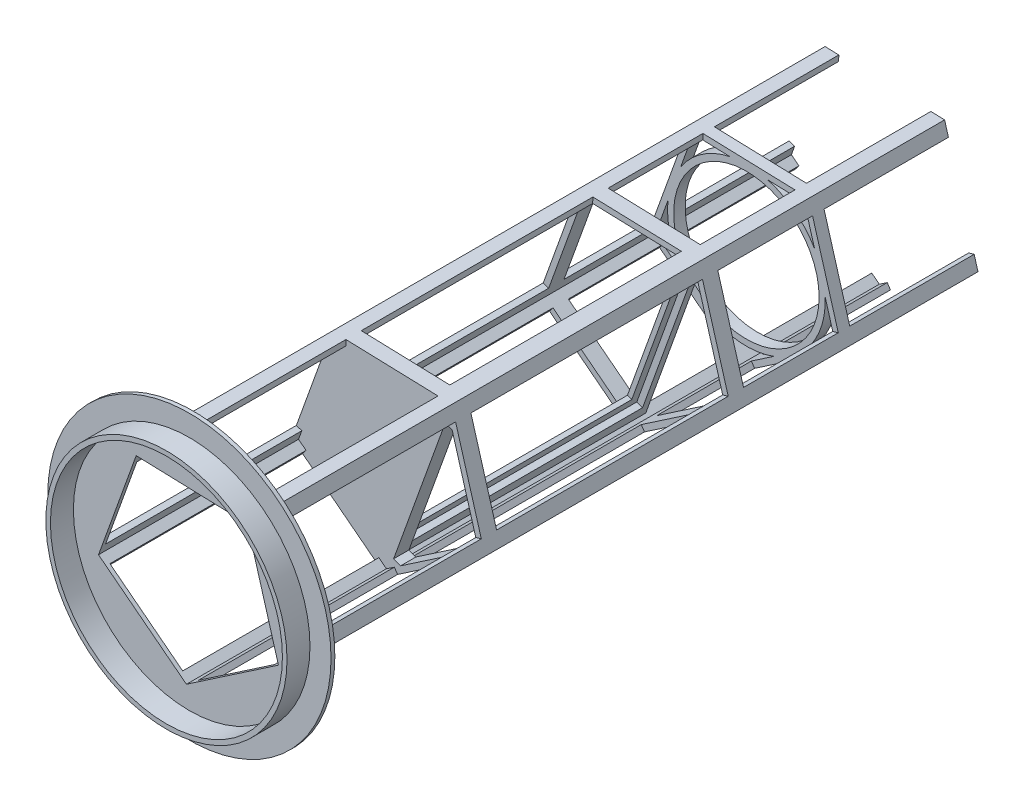
SolidWorks part; units mm, degrees
ref_plane "Front Plane" through (0, 0, 0) normal (0, 0, 1) x (1, 0, 0)
ref_plane "Top Plane" through (0, 0, 0) normal (0, 1, 0) x (1, 0, 0)
ref_plane "Right Plane" through (0, 0, 0) normal (1, 0, 0) x (0, 0, -1)
sketch "Sketch3" plane through (0, 0, 0) normal (0, 0, 1) x (1, 0, 0)
  line L0 (0, 0) -> (16.2851, 21.0012) construction
  line L1 (15.1489, 19.536) -> (-13.8986, 20.4445)
  line L2 (-13.8986, 20.4445) -> (-23.7387, -6.9006)
  line L3 (-23.7387, -6.9006) -> (-0.7728, -24.7093)
  line L4 (-0.7728, -24.7093) -> (23.2611, -8.3705)
  line L5 (0, 0) -> (29.9163, 0) construction
  line L6 (0, 0) -> (25.0057, -8.9983) construction
  line L10 (-0.8307, -26.5625) -> (25.0057, -8.9983)
  line L11 (25.0057, -8.9983) -> (16.2851, 21.0012)
  line L12 (16.2851, 21.0012) -> (-14.941, 21.9778)
  line L13 (-14.941, 21.9778) -> (-25.5191, -7.4182)
  line L14 (-25.5191, -7.4182) -> (-0.8307, -26.5625)
  line L15 (23.2611, -8.3705) -> (15.1489, 19.536)
  circle A0 centre (0, 0) radius 20 construction
  dimension "D2" = 40
extrude "Boss-Extrude2" add sketch "Sketch3" along normal blind 185
ref_plane "Plane1" through (0, 0, 92.5) normal (0, 0, 1) x (1, 0, 0)
sketch "Sketch4" plane through (0, 0, 0) normal (0, 0, -1) x (-1, 0, 0)
  line L0 (14.745, 18.0921) -> (16.1564, 18.6)
  line L1 (13.8986, 20.4445) -> (23.7387, -6.9006) construction
  line L2 (14.941, 21.9778) -> (25.5191, -7.4182) construction
  line L3 (24.3036, -4.0404) -> (22.8922, -4.5483)
  line L4 (22.8922, -4.5483) -> (14.745, 18.0921)
  line L5 (24.3036, -4.0404) -> (16.1564, 18.6)
  dimension "D1" = 2.5
  dimension "D2" = 2.5
extrude "Cut-Extrude1" cut sketch "Sketch4" against normal offset from surface (180 mm away) 5 up to face at (0, 0, 185)
ref_point "Point1"
ref_axis "Axis1" through (0, 0, 185) along (0, 0, 1)
pattern_circular "CirPattern1" count 5 over 360 about axis through (0, 0, 185) along (0, 0, 1) of "Cut-Extrude1"
ref_plane "Plane2" through (0, 0, 92.5) normal (0, 0, 1) x (1, 0, 0)
sketch "Sketch5" plane through (0, 0, 92.5) normal (0, 0, 1) x (1, 0, 0)
  line L0 (-2.0696, -25.6018) -> (14.7182, 21.0502) construction
  line L2 (-24.1133, -8.5083) -> (-1.8275, -25.7895) construction
  line L3 (23.2611, -8.3705) -> (0, 0) construction
  line L4 (-4.3961, -23.7977) -> (11.7756, 21.1422)
  line L8 (-2.0696, -25.6018) -> (-4.3961, -23.7977)
  line L10 (14.7182, 21.0502) -> (11.7756, 21.1422)
  line L11 (-2.0696, -25.6018) -> (14.7182, 21.0502)
  line L12 (-22.8004, 22.2236) -> (6.2471, 21.3151) construction
  dimension "D1" = 18
  dimension "D2" = 2.8
extrude "Boss-Extrude3" add sketch "Sketch5" along normal mid plane 64.5
sketch "Sketch6" plane through (0, 0, 124.75) normal (0, 0, 1) x (1, 0, 0)
  line L5 (-25.5191, -7.4182) -> (-0.8307, -26.5625)
  line L6 (-0.8307, -26.5625) -> (25.0057, -8.9983)
  line L7 (25.0057, -8.9983) -> (16.2851, 21.0012)
  line L8 (16.2851, 21.0012) -> (-14.941, 21.9778)
  line L9 (-14.941, 21.9778) -> (-25.5191, -7.4182)
  line L10 (-25.5191, -7.4182) -> (-0.8307, -26.5625)
  line L11 (-0.8307, -26.5625) -> (25.0057, -8.9983)
  line L12 (25.0057, -8.9983) -> (16.2851, 21.0012)
  line L13 (16.2851, 21.0012) -> (-14.941, 21.9778)
  line L14 (-14.941, 21.9778) -> (-25.5191, -7.4182)
  dimension "D1" = 0
extrude "Boss-Extrude4" add sketch "Sketch6" along normal blind 4
sketch "Sketch7" plane through (0, 0, 124.75) normal (0, 0, -1) x (-1, 0, 0)
  line L0 (-3.6897, -1.3278) -> (20.23, 7.2798) construction
  line L1 (-11.7756, 21.1422) -> (4.3961, -23.7977) construction
  line L2 (16.1564, 18.6) -> (24.3036, -4.0404) construction
  line L4 (19.0326, -2.4504) -> (13.1071, 14.0159)
  line L5 (0.2139, -9.2223) -> (-5.7115, 7.244)
  line L7 (19.0326, -2.4504) -> (-5.7115, 7.244) construction
  line L8 (0.2139, -9.2223) -> (13.1071, 14.0159) construction
  line L9 (9.6232, -5.8364) -> (3.6978, 10.63) construction
  line L11 (-11.7756, 21.1422) -> (4.3961, -23.7977) construction
  arc A0 (-5.7115, 7.244) -> (13.1071, 14.0159) centre (3.6978, 10.63) cw
  arc A1 (0.2139, -9.2223) -> (19.0326, -2.4504) centre (9.6232, -5.8364) ccw
  point P7 (6.6605, 2.3968)
  point P9 (13.0092, -15.2457)
  point P14 (0.3119, 20.0393)
  dimension "D1" = 37.5
  dimension "D2" = 20
  dimension "D3" = 1
extrude "Cut-Extrude2" cut sketch "Sketch7" against normal blind 2
sketch "Sketch8" plane through (6.3243, -2.2758, 0) normal (0.9409, -0.3386, 0) x (0, 0, -1)
  line L0 (-60.25, 0) -> (-124.75, 0) construction
  line L1 (-124.75, -23.2131) -> (-124.75, 23.2131) construction
  line L3 (-60.25, -23.2131) -> (-60.25, 23.2131) construction
  line L5 (-123, -20.5) -> (-123, 20.5)
  line L6 (-123, -20.5) -> (-62, -20.5)
  line L7 (-123, 20.5) -> (-62, 20.5)
  line L8 (-62, -20.5) -> (-62, 20.5)
  line L14 (-62, 20.5) -> (-123, -20.5) construction
  line L15 (-62, -20.5) -> (-123, 20.5) construction
  point P11 (-92.5, 0)
  point P14 (-92.5, 0)
  dimension "D1" = 61
  dimension "D2" = 41
extrude "Cut-Extrude3" cut sketch "Sketch8" against normal blind 1.6
sketch "Sketch9" plane through (4.8189, -1.7341, 0) normal (0.9409, -0.3386, 0) x (0, 0, -1)
  line L8 (-121, -18.5) -> (-64, -18.5)
  line L9 (-64, -18.5) -> (-64, 18.5)
  line L10 (-64, 18.5) -> (-121, 18.5)
  line L11 (-121, 18.5) -> (-121, -18.5)
  line L12 (-121, -18.5) -> (-64, -18.5)
  line L13 (-64, -18.5) -> (-64, 18.5)
  line L14 (-64, 18.5) -> (-121, 18.5)
  line L15 (-121, 18.5) -> (-121, -18.5)
  dimension "D1" = 2
extrude "Cut-Extrude4" cut sketch "Sketch9" against normal up to surface (1.2 mm away) up to face at (3.6897, -1.3278, 92.5)
sketch "Sketch10" plane through (0, 0, 60.25) normal (0, 0, -1) x (-1, 0, 0)
  line L25 (-23.2611, -8.3705) -> (0.7728, -24.7093)
  line L26 (0.7728, -24.7093) -> (23.7387, -6.9006)
  line L27 (23.7387, -6.9006) -> (13.8986, 20.4445)
  line L28 (13.8986, 20.4445) -> (-15.1489, 19.536)
  line L29 (-15.1489, 19.536) -> (-23.2611, -8.3705)
  line L30 (0.8307, -26.5625) -> (25.5191, -7.4182)
  line L31 (-25.0057, -8.9983) -> (0.8307, -26.5625)
  line L32 (-16.2851, 21.0012) -> (-25.0057, -8.9983)
  line L33 (14.941, 21.9778) -> (-16.2851, 21.0012)
  line L34 (25.5191, -7.4182) -> (14.941, 21.9778)
  line L40 (0.8307, -26.5625) -> (25.5191, -7.4182)
  line L41 (-25.0057, -8.9983) -> (0.8307, -26.5625)
  line L42 (-16.2851, 21.0012) -> (-25.0057, -8.9983)
  line L43 (14.941, 21.9778) -> (-16.2851, 21.0012)
  line L44 (25.5191, -7.4182) -> (14.941, 21.9778)
  dimension "D1" = 0
extrude "Boss-Extrude5" add sketch "Sketch10" against normal blind 4
sketch "Sketch11" plane through (0, 0, 60.25) normal (0, 0, -1) x (-1, 0, 0)
  line L0 (3.8621, -22.3137) -> (4.3961, -23.7977)
  line L1 (4.3961, -23.7977) -> (3.6676, -24.3627)
  line L2 (-11.2416, 19.6582) -> (-11.7756, 21.1422)
  line L3 (-11.7756, 21.1422) -> (-12.697, 21.1134)
  line L4 (21.7631, -8.4326) -> (3.8621, -22.3137)
  line L7 (3.8621, -22.3137) -> (-11.2416, 19.6582)
  line L9 (-14.1842, 19.5662) -> (1.5355, -24.1178)
  line L10 (-14.1842, 19.5662) -> (1.5355, -24.1178)
  line L11 (-12.697, 21.1134) -> (11.3529, 21.8656) construction
  line L13 (3.8621, -22.3137) -> (-11.2416, 19.6582) construction
  line L18 (22.6823, -9.618) -> (3.6676, -24.3627) construction
  line L19 (3.8621, -22.3137) -> (-11.2416, 19.6582)
  line L27 (-11.2416, 19.6582) -> (11.3998, 20.3663)
  line L31 (1.5355, -24.1178) -> (2.7484, -23.1773)
  line L33 (1.5355, -24.1178) -> (2.7484, -23.1773)
  line L35 (2.7484, -23.1773) -> (3.6676, -24.3627)
  line L37 (2.7484, -23.1773) -> (3.6676, -24.3627)
  line L39 (3.6676, -24.3627) -> (22.6823, -9.618)
  line L41 (22.6823, -9.618) -> (21.7631, -8.4326)
  line L43 (11.3998, 20.3663) -> (11.3529, 21.8656)
  line L45 (11.3529, 21.8656) -> (-12.697, 21.1134)
  line L47 (-12.697, 21.1134) -> (-12.6502, 19.6141)
  line L48 (-12.697, 21.1134) -> (-12.6502, 19.6141)
  line L49 (-12.6502, 19.6141) -> (-14.1842, 19.5662)
  line L50 (-12.6502, 19.6141) -> (-14.1842, 19.5662)
  dimension "D1" = 0
ref_plane "Plane3" through (0, 0, 32.5) normal (0, 0, 1) x (1, 0, 0)
sketch "Sketch14" plane through (0, 0, 32.5) normal (0, 0, 1) x (1, 0, 0)
  line L5 (-25.5191, -7.4182) -> (-0.8307, -26.5625)
  line L6 (-0.8307, -26.5625) -> (25.0057, -8.9983)
  line L7 (25.0057, -8.9983) -> (16.2851, 21.0012)
  line L8 (16.2851, 21.0012) -> (-14.941, 21.9778)
  line L9 (-14.941, 21.9778) -> (-25.5191, -7.4182)
  line L11 (-0.8307, -26.5625) -> (25.0057, -8.9983)
  line L12 (25.0057, -8.9983) -> (16.2851, 21.0012)
  line L16 (23.2611, -8.3705) -> (15.3259, -13.7651)
  line L18 (-0.7728, -24.7093) -> (-8.3554, -18.8294)
  line L20 (-23.7387, -6.9006) -> (-20.4898, 2.1279)
  line L22 (-13.8986, 20.4445) -> (-4.308, 20.1445)
  line L24 (15.1489, 19.536) -> (17.8273, 10.3221)
  line L25 (7.1625, -19.3147) -> (-0.7728, -24.7093)
  line L26 (20.5827, 0.8433) -> (23.2611, -8.3705)
  line L27 (5.5584, 19.8359) -> (15.1489, 19.536)
  line L28 (-17.1475, 11.416) -> (-13.8986, 20.4445)
  line L29 (-16.1561, -12.7805) -> (-23.7387, -6.9006)
  line L30 (16.2851, 21.0012) -> (-14.941, 21.9778)
  line L31 (-14.941, 21.9778) -> (-25.5191, -7.4182)
  line L32 (-25.5191, -7.4182) -> (-0.8307, -26.5625)
  circle A3 centre (0, 0) radius 19
  arc A8 (15.3259, -13.7651) -> (20.5827, 0.8433) centre (0, 0) ccw
  circle A9 centre (0, 0) radius 20.6 construction
  arc A10 (17.8273, 10.3221) -> (5.5584, 19.8359) centre (0, 0) ccw
  arc A11 (-4.308, 20.1445) -> (-17.1475, 11.416) centre (0, 0) ccw
  arc A12 (-20.4898, 2.1279) -> (-16.1561, -12.7805) centre (0, 0) ccw
  arc A13 (-8.3554, -18.8294) -> (7.1625, -19.3147) centre (0, 0) ccw
  dimension "D2" = 38
  dimension "D1" = 0
  dimension "D3" = 1.6
extrude "Boss-Extrude8" add sketch "Sketch14" along normal blind 3
ref_plane "Plane4" through (0, 0, 29.5) normal (0, 0, -1) x (-1, 0, 0)
sketch "Sketch15" plane through (0, 0, 29.5) normal (0, 0, -1) x (-1, 0, 0)
  line L0 (-23.2611, -8.3705) -> (0.7728, -24.7093)
  line L1 (0.7728, -24.7093) -> (23.7387, -6.9006)
  line L2 (23.7387, -6.9006) -> (13.8986, 20.4445)
  line L3 (13.8986, 20.4445) -> (-15.1489, 19.536)
  line L4 (-15.1489, 19.536) -> (-23.2611, -8.3705)
  line L5 (0.8307, -26.5625) -> (25.5191, -7.4182)
  line L6 (-25.0057, -8.9983) -> (0.8307, -26.5625)
  line L7 (-16.2851, 21.0012) -> (-25.0057, -8.9983)
  line L8 (14.941, 21.9778) -> (-16.2851, 21.0012)
  line L9 (25.5191, -7.4182) -> (14.941, 21.9778)
  line L10 (0.8307, -26.5625) -> (25.5191, -7.4182)
  line L11 (-25.0057, -8.9983) -> (0.8307, -26.5625)
  line L12 (-16.2851, 21.0012) -> (-25.0057, -8.9983)
  line L13 (14.941, 21.9778) -> (-16.2851, 21.0012)
  line L14 (25.5191, -7.4182) -> (14.941, 21.9778)
  dimension "D1" = 0
sketch "Sketch29" plane through (0, 0, 185) normal (0, 0, 1) x (1, 0, 0)
  line L5 (-25.5191, -7.4182) -> (-0.8307, -26.5625)
  line L6 (-0.8307, -26.5625) -> (25.0057, -8.9983)
  line L7 (25.0057, -8.9983) -> (16.2851, 21.0012)
  line L8 (16.2851, 21.0012) -> (-14.941, 21.9778)
  line L9 (-14.941, 21.9778) -> (-25.5191, -7.4182)
  line L10 (-25.5191, -7.4182) -> (-0.8307, -26.5625)
  line L11 (-0.8307, -26.5625) -> (25.0057, -8.9983)
  line L12 (25.0057, -8.9983) -> (16.2851, 21.0012)
  line L13 (16.2851, 21.0012) -> (-14.941, 21.9778)
  line L14 (-14.941, 21.9778) -> (-25.5191, -7.4182)
  dimension "D1" = 0
extrude "Boss-Extrude13" add sketch "Sketch29" along normal blind 2
sketch "Sketch30" plane through (0, 0, 187) normal (0, 0, 1) x (1, 0, 0)
  line L0 (25.0057, -8.9983) -> (-20.23, 7.2798) construction
  line L1 (-14.941, 21.9778) -> (-25.5191, -7.4182) construction
  line L2 (3.1542, -17.0767) -> (-13.3121, -11.1513)
  line L3 (18.5086, -9.8487) -> (20.5401, -4.2031)
  line L4 (-20.5401, 4.2031) -> (-18.5086, 9.8487)
  line L5 (13.3121, 11.1513) -> (-3.1542, 17.0767)
  line L6 (14.4454, -21.1398) -> (-14.4454, 21.1398) construction
  line L7 (-24.6033, -7.0881) -> (24.6033, 7.0881) construction
  line L8 (19.5243, -7.0259) -> (-19.5243, 7.0259) construction
  arc A0 (18.5086, -9.8487) -> (3.1542, -17.0767) centre (7.2174, -5.7855) cw
  arc A1 (-18.5086, 9.8487) -> (-3.1542, 17.0767) centre (-7.2174, 5.7855) cw
  arc A2 (-13.3121, -11.1513) -> (-20.5401, 4.2031) centre (-9.2489, 0.1399) cw
  arc A3 (20.5401, -4.2031) -> (13.3121, 11.1513) centre (9.2489, -0.1399) ccw
  point P5 (0, 0)
  dimension "D3" = 12
  dimension "D1" = 30
  dimension "D2" = 41.5
extrude "Cut-Extrude8" [suppressed] cut sketch "Sketch30" against normal blind 0.6
sketch "Sketch31" [suppressed] plane through (0, 0, 186.4) normal (0, 0, 1) x (1, 0, 0)
  line L0 (25.0057, -8.9983) -> (0, 0) construction
  line L1 (12.0432, 0.9801) -> (8.6573, -8.4292)
  line L2 (12.0432, 0.9801) -> (-8.6573, 8.4292)
  line L3 (8.6573, -8.4292) -> (-12.0432, -0.9801)
  line L4 (-8.6573, 8.4292) -> (-12.0432, -0.9801)
  line L5 (12.0432, 0.9801) -> (-12.0432, -0.9801) construction
  line L6 (8.6573, -8.4292) -> (-8.6573, 8.4292) construction
  line L7 (-10.3503, 3.7246) -> (10.3503, -3.7246) construction
  dimension "D1" = 22
  dimension "D2" = 10
extrude "Cut-Extrude9" [suppressed] cut sketch "Sketch31" against normal up to surface (1.4 mm away) up to face at (0, 0, 185)
sketch "Sketch32" [suppressed] plane through (0, 0, 187) normal (0, 0, 1) x (1, 0, 0)
  line L0 (0, 0) -> (-36.3954, 13.0969) construction
  line L1 (-22.7695, 0.2228) -> (-21.2398, -0.3276)
  line L3 (-14.941, 21.9778) -> (-25.5191, -7.4182) construction
  line L4 (-17.6906, 14.3368) -> (-16.1609, 13.7863)
  line L5 (-18.5086, 9.8487) -> (-20.5401, 4.2031) construction
  line L6 (-18.5086, 9.8487) -> (-20.5401, 4.2031)
  line L7 (-17.6906, 14.3368) -> (-22.7695, 0.2228)
  arc A0 (-20.5401, 4.2031) -> (-13.3121, -11.1513) centre (-9.2489, 0.1399) ccw construction
  arc A1 (-20.5401, 4.2031) -> (-13.3121, -11.1513) centre (-9.2489, 0.1399) ccw construction
  arc A3 (-3.1542, 17.0767) -> (-18.5086, 9.8487) centre (-7.2174, 5.7855) ccw construction
  arc A4 (-16.1609, 13.7863) -> (-18.5086, 9.8487) centre (-7.2174, 5.7855) ccw
  arc A5 (-20.5401, 4.2031) -> (-21.2398, -0.3276) centre (-9.2489, 0.1399) ccw
  dimension "D1" = 7.5
extrude "Cut-Extrude11" [suppressed] cut sketch "Sketch32" against normal up to surface (0.6 mm away) up to face at (-13.7489, 20.2244, 0)
sketch "Sketch34" [suppressed] plane through (0, 0, 186.4) normal (0, 0, 1) x (1, 0, 0)
  line L0 (-22.7695, 0.2228) -> (-17.6906, 14.3368)
  line L1 (-22.7695, 0.2228) -> (-22.0638, -0.0311)
  line L2 (-17.6906, 14.3368) -> (-16.9849, 14.0828)
  line L3 (-22.0638, -0.0311) -> (-16.9849, 14.0828)
  line L4 (-13.3121, -11.1513) -> (3.1542, -17.0767)
  line L5 (18.5086, -9.8487) -> (20.5401, -4.2031)
  line L6 (13.3121, 11.1513) -> (-3.1542, 17.0767)
  line L7 (-18.5086, 9.8487) -> (-20.5401, 4.2031)
  line L8 (-13.3121, -11.1513) -> (3.1542, -17.0767) construction
  line L9 (18.5086, -9.8487) -> (20.5401, -4.2031) construction
  line L10 (13.3121, 11.1513) -> (-3.1542, 17.0767) construction
  line L11 (-18.5086, 9.8487) -> (-20.5401, 4.2031) construction
  arc A4 (3.1542, -17.0767) -> (18.5086, -9.8487) centre (7.2174, -5.7855) ccw
  arc A5 (20.5401, -4.2031) -> (13.3121, 11.1513) centre (9.2489, -0.1399) ccw
  arc A6 (-3.1542, 17.0767) -> (-18.5086, 9.8487) centre (-7.2174, 5.7855) ccw
  arc A7 (-20.5401, 4.2031) -> (-13.3121, -11.1513) centre (-9.2489, 0.1399) ccw
  arc A8 (3.1542, -17.0767) -> (18.5086, -9.8487) centre (7.2174, -5.7855) ccw construction
  arc A9 (20.5401, -4.2031) -> (13.3121, 11.1513) centre (9.2489, -0.1399) ccw construction
  arc A10 (-3.1542, 17.0767) -> (-18.5086, 9.8487) centre (-7.2174, 5.7855) ccw construction
  arc A11 (-20.5401, 4.2031) -> (-13.3121, -11.1513) centre (-9.2489, 0.1399) ccw construction
  dimension "D1" = 0
sketch "Sketch38" plane through (0, 0, 124.75) normal (0, 0, -1) x (-1, 0, 0)
  line L5 (13.8986, 20.4445) -> (-15.1489, 19.536)
  line L6 (-15.1489, 19.536) -> (-23.2611, -8.3705)
  line L7 (-23.2611, -8.3705) -> (0.7728, -24.7093)
  line L8 (0.7728, -24.7093) -> (23.7387, -6.9006)
  line L9 (23.7387, -6.9006) -> (13.8986, 20.4445)
  line L11 (-16.3988, 15.2363) -> (-23.2611, -8.3705)
  line L12 (-23.2611, -8.3705) -> (-2.9303, -22.1919)
  line L16 (-1.0956, -21.5316) -> (-2.9303, -22.1919)
  line L17 (0.03, -24.6596) -> (-15.6897, 19.0244)
  line L18 (-1.0956, -21.5316) -> (-14.5641, 15.8965)
  line L19 (-14.5641, 15.8965) -> (-16.3988, 15.2363)
  dimension "D3" = 1.6
  dimension "D4" = 1.6
  dimension "D1" = 0
  dimension "D2" = 1.6
extrude "Cut-Extrude14" cut sketch "Sketch38" against normal up to surface (4 mm away) up to face at (0, 0, 128.75)
sketch "Sketch40" plane through (-18.8186, 6.7719, 0) normal (0.9409, -0.3386, 0) x (0, 0, -1)
  line L0 (-185, 14.5309) -> (-185, -14.5309) construction
  line L1 (-185, 7.5) -> (-183.5, 7.5)
  line L2 (-185, 7.5) -> (-185, -7.5)
  line L3 (-185, -7.5) -> (-183.5, -7.5)
  line L4 (-183.5, 7.5) -> (-183.5, -7.5)
  line L5 (-183.5, 0) -> (-185, 0) construction
  point P9 (-185, 0)
  dimension "D1" = 15
  dimension "D2" = 1.5
ref_plane "Plane5" through (14.5641, 15.8965, 124.75) normal (0.3386, 0.9409, 0) x (0.9409, -0.3386, 0)
sketch "Sketch42" plane through (0, 0, 128.75) normal (0, 0, 1) x (1, 0, 0)
  line L0 (-20.23, 7.2798) -> (0, 0) construction
  line L1 (-16.1564, 18.6) -> (-24.3036, -4.0404) construction
  line L2 (5.4365, -16.774) -> (-14.8782, -9.4637) construction
  line L3 (5.4365, -16.774) -> (14.8782, 9.4637) construction
  line L4 (-14.8782, -9.4637) -> (-5.4365, 16.774) construction
  line L5 (14.8782, 9.4637) -> (-5.4365, 16.774) construction
  line L6 (5.4365, -16.774) -> (-5.4365, 16.774) construction
  line L7 (-14.8782, -9.4637) -> (14.8782, 9.4637) construction
  line L8 (-3.9066, 13.524) -> (11.6282, 7.9338) construction
  line L9 (4.7208, 13.1189) -> (-4.7208, -13.1189) construction
  line L10 (2.2472, -13.2032) -> (-10.1449, -8.7439) construction
  line L11 (-1.5355, -24.1178) -> (14.1842, 19.5662) construction
  line L12 (-1.5355, -24.1178) -> (14.1842, 19.5662)
  line L13 (12.891, 3.9416) -> (6.1392, -14.8212) construction
  line L14 (12.891, 3.9416) -> (10.6328, 4.7542) construction
  line L15 (6.1392, -14.8212) -> (3.881, -14.0086) construction
  line L16 (10.6328, 4.7542) -> (3.881, -14.0086) construction
  circle A0 centre (11.6282, 7.9338) radius 1
  circle A1 centre (-3.9066, 13.524) radius 1
  circle A2 centre (2.2472, -13.2032) radius 1
  circle A3 centre (-10.1449, -8.7439) radius 1
  point P1 (3.8608, 10.7289)
  point P2 (0, 0)
  point P19 (-3.9488, -10.9735)
  dimension "D4" = 2
  dimension "D7" = 2
  dimension "D1" = 21.59
  dimension "D2" = 27.8848
  dimension "D3" = 16.51
  dimension "D5" = 2.54
  dimension "D6" = 13.17
  dimension "D8" = 2.28
  dimension "D9" = 2.4
sketch "Sketch43" plane through (0, 0, 128.75) normal (0, 0, 1) x (1, 0, 0)
  line L1 (10.8306, 5.5214) -> (12.5507, 10.3013)
  line L2 (12.891, 3.9416) -> (10.6328, 4.7542) construction
  line L3 (12.891, 3.9416) -> (10.6328, 4.7542)
  line L4 (1.0956, -21.5316) -> (14.5641, 15.8965) construction
  arc A0 (12.5507, 10.3013) -> (10.8306, 5.5214) centre (11.6282, 7.9338) cw
  point P4 (12.5507, 10.3013)
  line M27 (1.0956, -21.5316) -> (14.5641, 15.8965)
  dimension "D1" = 2.5409
extrude "Boss-Extrude15" [suppressed] add sketch "Sketch43" against normal up to surface (4 mm away) contours A0 M27 up to face at (11.7736, -4.2367, 124.75)
sketch "Sketch44" plane through (0, 0, 128.75) normal (0, 0, 1) x (1, 0, 0)
  circle A0 centre (-10.1449, -8.7439) radius 1 construction
  circle A1 centre (-3.9066, 13.524) radius 1 construction
  circle A2 centre (-10.1449, -8.7439) radius 1
  circle A3 centre (-3.9066, 13.524) radius 1
extrude "Cut-Extrude18" [suppressed] cut sketch "Sketch42" against normal blind 3.5 contours A0 | A2
extrude "Cut-Extrude19" [suppressed] cut sketch "Sketch44" against normal blind 1.5
sketch "Sketch45" plane through (0, 0, 128.75) normal (0, 0, 1) x (1, 0, 0)
  line L0 (-2.5743, -18.735) -> (9.9537, 16.0795) construction
  line L1 (-2.5743, -18.735) -> (9.9537, 16.0795) construction
  line L2 (13.2655, 17.0133) -> (-0.6169, -21.5649) construction
  line L3 (13.2655, 17.0133) -> (-0.6169, -21.5649) construction
  line L4 (-4.3961, -23.7977) -> (11.7756, 21.1422)
  line L5 (11.7756, 21.1422) -> (14.7182, 21.0502)
  line L6 (14.7182, 21.0502) -> (-2.0696, -25.6018)
  line L7 (-2.0696, -25.6018) -> (-4.3961, -23.7977)
  line L8 (-22.6823, -9.618) -> (-3.6676, -24.3627) construction
  line L11 (12.697, 21.1134) -> (-11.3529, 21.8656) construction
sketch "Sketch46" plane through (0, 0, 128.75) normal (0, 0, 1) x (1, 0, 0)
  line L0 (-8.1098, 21.7641) -> (-20.1403, -11.5891)
  line L1 (-8.1098, 21.7641) -> (-4.6098, 21.6547)
  line L2 (-20.1403, -11.5891) -> (-17.3745, -13.7339)
  line L3 (-4.6098, 21.6547) -> (-17.3745, -13.7339)
  line L4 (-16.1564, 18.6) -> (-24.3036, -4.0404) construction
  line L5 (-1.5355, -24.1178) -> (14.1842, 19.5662) construction
  line L6 (-1.5355, -24.1178) -> (14.1842, 19.5662)
  line L8 (12.697, 21.1134) -> (-11.3529, 21.8656) construction
  line L9 (-22.6823, -9.618) -> (-3.6676, -24.3627) construction
  dimension "D1" = 3.5
  dimension "D2" = 3.5
  dimension "D3" = 6.5
sketch "Sketch49" plane through (0, 0, 126.75) normal (0, 0, -1) x (-1, 0, 0)
  line L0 (-2.7488, -0.9892) -> (16.0698, 5.7828) construction
  line L1 (-5.7115, 7.244) -> (0.2139, -9.2223) construction
  line L2 (19.0326, -2.4504) -> (13.1071, 14.0159) construction
  line L3 (12.4006, 7.1193) -> (14.0935, 2.4146) construction
  line L4 (15.2234, 8.1351) -> (16.9163, 3.4304)
  line L5 (9.5778, 6.1035) -> (11.2707, 1.3988)
  arc A0 (15.2234, 8.1351) -> (9.5778, 6.1035) centre (12.4006, 7.1193) ccw
  arc A1 (11.2707, 1.3988) -> (16.9163, 3.4304) centre (14.0935, 2.4146) ccw
  point P8 (13.247, 4.767)
  dimension "D1" = 6
  dimension "D2" = 5
sketch "Sketch54" plane through (4.8189, -1.7341, 0) normal (0.9409, -0.3386, 0) x (0, 0, -1)
  line L0 (-62, 20.5) -> (-123, 20.5) construction
  line L1 (-123, 20.5) -> (-123, -20.5) construction
  line L2 (-64, 0) -> (-121, 0) construction
  line L3 (-64, -18.5) -> (-64, 18.5) construction
  line L4 (-121, 18.5) -> (-121, -18.5) construction
  line L5 (-92.5, 18.5) -> (-92.5, -18.5) construction
  line L6 (-64, 18.5) -> (-121, 18.5) construction
  line L7 (-121, -18.5) -> (-64, -18.5) construction
  circle A0 centre (-122, 19.5) radius 0.5
  circle A1 centre (-122, -19.5) radius 0.5
  circle A2 centre (-63, -19.5) radius 0.5
  circle A3 centre (-63, 19.5) radius 0.5
  dimension "D1" = 1
  dimension "D2" = 1
  dimension "D3" = 1
ref_plane "Plane8" through (15.2997, 42.5167, 0) normal (-0.3386, -0.9409, 0) x (-0.9409, 0.3386, 0)
sketch "Sketch55" plane through (0, 0, 187) normal (0, 0, 1) x (1, 0, 0)
  line L0 (-14.941, 21.9778) -> (-25.5191, -7.4182) construction
  line L1 (-25.5191, -7.4182) -> (-0.8307, -26.5625) construction
  line L2 (-0.8307, -26.5625) -> (25.0057, -8.9983) construction
  line L3 (25.0057, -8.9983) -> (16.2851, 21.0012) construction
  line L4 (16.2851, 21.0012) -> (-14.941, 21.9778) construction
  line L5 (-14.941, 21.9778) -> (-25.5191, -7.4182)
  line L6 (-25.5191, -7.4182) -> (-0.8307, -26.5625)
  line L7 (-0.8307, -26.5625) -> (25.0057, -8.9983)
  line L8 (25.0057, -8.9983) -> (16.2851, 21.0012)
  line L9 (16.2851, 21.0012) -> (-14.941, 21.9778)
  circle A0 centre (0, 0) radius 37
  point P3 (0, -37)
  dimension "D1" = 37
extrude "Boss-Extrude17" add sketch "Sketch55" against normal up to surface (7 mm away) up to face at (0.6486, 20.7399, 180)
sketch "Sketch56" plane through (0, 0, 187) normal (0, 0, 1) x (1, 0, 0)
  circle A1 centre (0, 0) radius 31.5
  circle A2 centre (0, 0) radius 37 construction
  circle A3 centre (0, 0) radius 37
  circle A4 centre (0, 0) radius 30.3
  circle M1 centre (0, 0) radius 37
  dimension "D1" = 63
  dimension "D2" = 1.2
extrude "Cut-Extrude20" cut sketch "Sketch56" against normal offset from surface (6 mm away) 1 contours A1 M1 | A4 region at (-35.9535, 0, 187) region at (0, 0, 187) up to face at (0, 0, 180)
